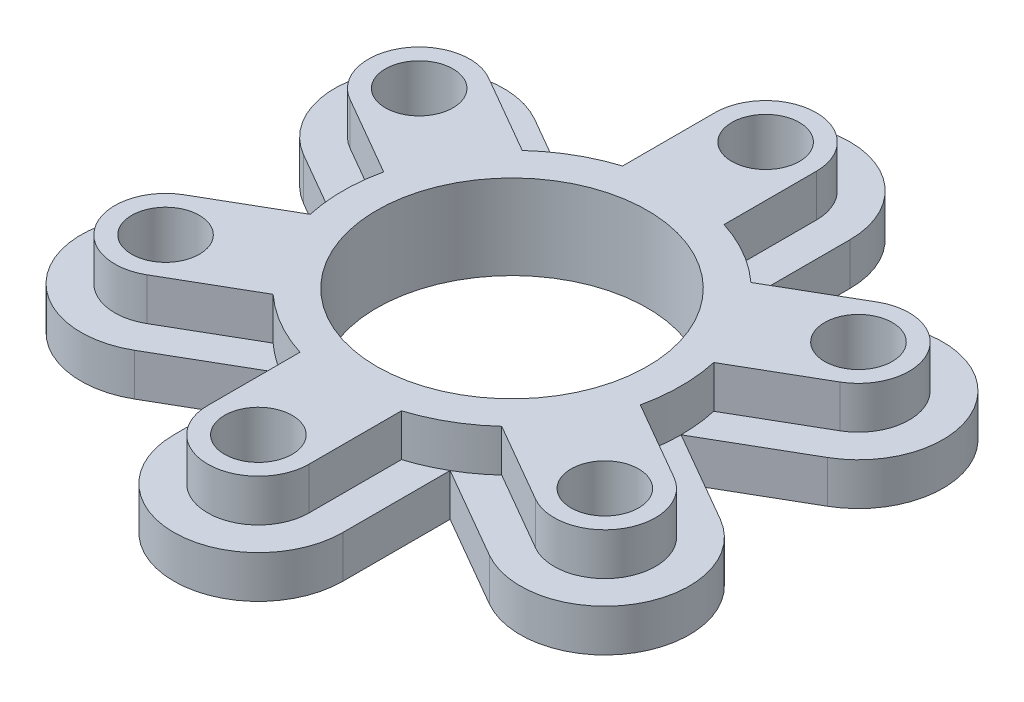
SolidWorks part; units mm, degrees
ref_plane "Front Plane" through (0, 0, 0) normal (0, 0, 1) x (1, 0, 0)
ref_plane "Top Plane" through (0, 0, 0) normal (0, 1, 0) x (1, 0, 0)
ref_plane "Right Plane" through (0, 0, 0) normal (1, 0, 0) x (0, 0, -1)
sketch "Sketch1" plane through (0, 0, 0) normal (0, 1, 0) x (1, 0, 0)
  line L0 (0, -1000) -> (0, 49000) construction
  line L1 (-10, 30) -> (-10, 17.3205)
  line L2 (10, 30) -> (10, 17.3205)
  line L3 (-6, 30) -> (-6, 19.0788)
  line L4 (6, 30) -> (6, 19.0788)
  line L5 (20.9808, 23.6603) -> (10, 17.3205)
  line L6 (30.9808, 6.3397) -> (20, 0)
  line L7 (22.9808, 20.1962) -> (13.5227, 14.7355)
  line L8 (28.9808, 9.8038) -> (19.5227, 4.3432)
  line L9 (30.9808, -6.3397) -> (20, 0)
  line L10 (20.9808, -23.6603) -> (10, -17.3205)
  line L11 (28.9808, -9.8038) -> (19.5227, -4.3432)
  line L12 (22.9808, -20.1962) -> (13.5227, -14.7355)
  line L13 (10, -30) -> (10, -17.3205)
  line L14 (-10, -30) -> (-10, -17.3205)
  line L15 (6, -30) -> (6, -19.0788)
  line L16 (-6, -30) -> (-6, -19.0788)
  line L17 (-20.9808, -23.6603) -> (-10, -17.3205)
  line L18 (-30.9808, -6.3397) -> (-20, 0)
  line L19 (-22.9808, -20.1962) -> (-13.5227, -14.7355)
  line L20 (-28.9808, -9.8038) -> (-19.5227, -4.3432)
  line L21 (-30.9808, 6.3397) -> (-20, 0)
  line L22 (-20.9808, 23.6603) -> (-10, 17.3205)
  line L23 (-28.9808, 9.8038) -> (-19.5227, 4.3432)
  line L24 (-22.9808, 20.1962) -> (-13.5227, 14.7355)
  circle A0 centre (0, 0) radius 16
  arc A1 (-6, 19.0788) -> (-10, 17.3205) centre (0, 0) ccw
  circle A2 centre (0, 30) radius 4
  arc A3 (6, 30) -> (-6, 30) centre (0, 30) ccw
  arc A4 (10, 30) -> (-10, 30) centre (0, 30) ccw
  arc A5 (10, 17.3205) -> (6, 19.0788) centre (0, 0) ccw
  arc A6 (13.5227, 14.7355) -> (10, 17.3205) centre (0, 0) ccw
  circle A7 centre (25.9808, 15) radius 4
  arc A8 (28.9808, 9.8038) -> (22.9808, 20.1962) centre (25.9808, 15) ccw
  arc A9 (30.9808, 6.3397) -> (20.9808, 23.6603) centre (25.9808, 15) ccw
  arc A10 (20, 0) -> (19.5227, 4.3432) centre (0, 0) ccw
  arc A11 (19.5227, -4.3432) -> (20, 0) centre (0, 0) ccw
  circle A12 centre (25.9808, -15) radius 4
  arc A13 (22.9808, -20.1962) -> (28.9808, -9.8038) centre (25.9808, -15) ccw
  arc A14 (20.9808, -23.6603) -> (30.9808, -6.3397) centre (25.9808, -15) ccw
  arc A15 (10, -17.3205) -> (13.5227, -14.7355) centre (0, 0) ccw
  arc A16 (6, -19.0788) -> (10, -17.3205) centre (0, 0) ccw
  circle A17 centre (0, -30) radius 4
  arc A18 (-6, -30) -> (6, -30) centre (0, -30) ccw
  arc A19 (-10, -30) -> (10, -30) centre (0, -30) ccw
  arc A20 (-10, -17.3205) -> (-6, -19.0788) centre (0, 0) ccw
  arc A21 (-13.5227, -14.7355) -> (-10, -17.3205) centre (0, 0) ccw
  circle A22 centre (-25.9808, -15) radius 4
  arc A23 (-28.9808, -9.8038) -> (-22.9808, -20.1962) centre (-25.9808, -15) ccw
  arc A24 (-30.9808, -6.3397) -> (-20.9808, -23.6603) centre (-25.9808, -15) ccw
  arc A25 (-20, 0) -> (-19.5227, -4.3432) centre (0, 0) ccw
  arc A26 (-19.5227, 4.3432) -> (-20, 0) centre (0, 0) ccw
  circle A27 centre (-25.9808, 15) radius 4
  arc A28 (-22.9808, 20.1962) -> (-28.9808, 9.8038) centre (-25.9808, 15) ccw
  arc A29 (-20.9808, 23.6603) -> (-30.9808, 6.3397) centre (-25.9808, 15) ccw
  arc A30 (-10, 17.3205) -> (-13.5227, 14.7355) centre (0, 0) ccw
  point P67 (0, 0)
  dimension "D1" = 32
  dimension "D2" = 40
  dimension "D3" = 20
  dimension "D4" = 8
  dimension "D5" = 12
  dimension "D6" = 30
  dimension "D7" = 6
extrude "Boss-Extrude1" add sketch "Sketch1" along normal blind 10 contours L0 A18 L15 A16 A15 L12 A13 L11 A11 A10 L8 A8 L7 A6 A5 L4 A3 A2 A0 A17 A7 A12 | A18 L0 A17 A0 A2 A3 L3 A1 A30 L24 A28 L23 A26 A25 L20 A23 L19 A21 A20 L16 A27 A22 region at (-3.6856, 0, 33.6856) region at (0.7878, 0, 35)
extrude "Boss-Extrude2" add sketch "Sketch1<5>" along normal blind 5 contours A25 L18 A24 L17 A21 L19 A23 L20 | A10 L6 A9 L5 A6 L7 A8 L8 | A15 L10 A14 L9 A11 L11 A13 L12 | A18 L15 A16 L13 A19 L14 A20 L16 | A4 L1 A1 L3 A3 L4 A5 L2 | A29 L21 A26 L23 A28 L24 A30 L22 region at (15.6707, 0, -20.1781) region at (-20.2387, 0, 2.2241) region at (25.3101, 0, 3.4821)
sketch "Sketch1<5>" plane through (0, 0, 0) normal (0, 1, 0) x (1, 0, 0) same geometry as "Sketch1"
